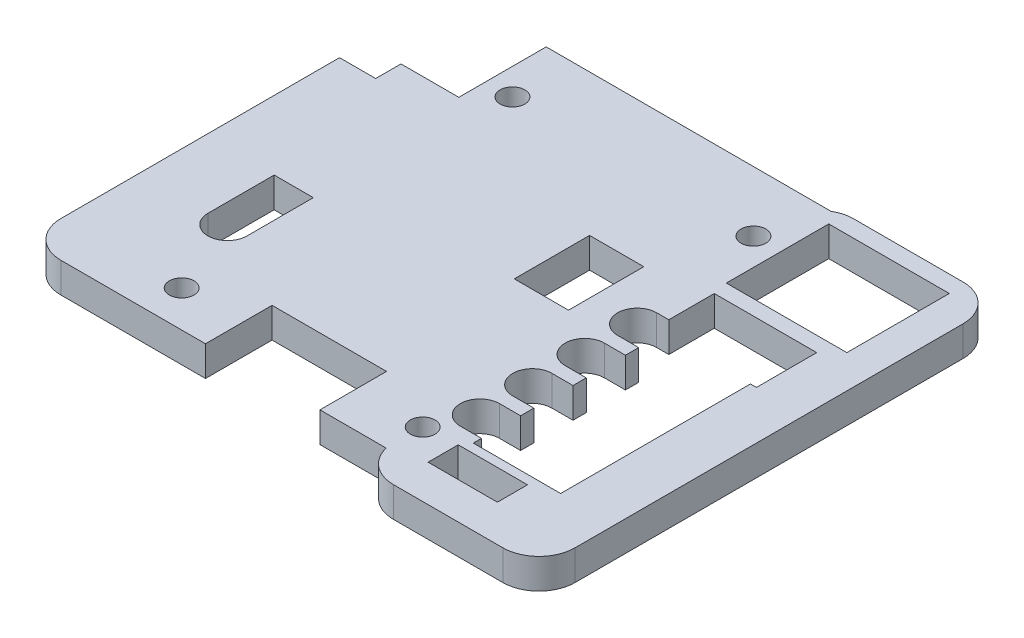
SolidWorks part; units mm, degrees
ref_plane "前视基准面" through (0, 0, 0) normal (0, 0, 1) x (1, 0, 0)
ref_plane "上视基准面" through (0, 0, 0) normal (0, 1, 0) x (1, 0, 0)
ref_plane "右视基准面" through (0, 0, 0) normal (1, 0, 0) x (0, 0, -1)
sketch "草图1" plane through (0, 0, 0) normal (0, 1, 0) x (1, 0, 0)
  line L0 (6, 0.3) -> (143.8, 0.3)
  line L1 (6, 0) -> (143.8, 0) construction
  line L2 (0, -6) -> (0, -68.8) construction
  line L3 (6, -74.8) -> (143.8, -74.8) construction
  line L4 (149.8, -6) -> (149.8, -68.8) construction
  line L5 (150.1, -6) -> (150.1, -68.8)
  line L6 (6, -75.1) -> (143.8, -75.1)
  line L7 (-0.3, -6) -> (-0.3, -68.8)
  arc A0 (143.8, 0) -> (149.8, -6) centre (143.8, -6) cw construction
  arc A1 (143.8, -74.8) -> (149.8, -68.8) centre (143.8, -68.8) ccw construction
  arc A2 (0, -68.8) -> (6, -74.8) centre (6, -68.8) ccw construction
  arc A3 (6, 0) -> (0, -6) centre (6, -6) ccw construction
  arc A4 (143.8, 0.3) -> (150.1, -6) centre (143.8, -6) cw
  arc A5 (143.8, -75.1) -> (150.1, -68.8) centre (143.8, -68.8) ccw
  arc A6 (-0.3, -68.8) -> (6, -75.1) centre (6, -68.8) ccw
  arc A7 (6, 0.3) -> (-0.3, -6) centre (6, -6) ccw
  point P7 (149.8, 0)
  point P12 (0, -74.8)
  point P15 (0, 0)
  dimension "D3" = 6
  dimension "D1" = 74.8
  dimension "D2" = 149.8
  dimension "D4" = 0.3
sketch "草图2" plane through (0, 0, 0) normal (0, -1, 0) x (-1, 0, 0)
  line L0 (-122.6, -55.35) -> (-108.9, -55.35) construction
  line L1 (-122.6, -69.85) -> (-108.9, -69.85) construction
  line L2 (-122.6, -69.85) -> (-122.6, -63.95) construction
  line L3 (-122.6, -63.95) -> (-108.9, -63.95) construction
  line L4 (-108.9, -69.85) -> (-108.9, -63.95) construction
  line L5 (-135.3, -1.25) -> (-35.3, -1.25) construction
  line L6 (-135.3, -1.25) -> (-135.3, -73.55) construction
  line L7 (-135.3, -73.55) -> (-35.3, -73.55) construction
  line L8 (-35.3, -1.25) -> (-35.3, -73.55) construction
  line L9 (-108.9, -61.25) -> (-108.9, -55.35) construction
  line L10 (-122.6, -61.25) -> (-108.9, -61.25) construction
  line L11 (-122.6, -61.25) -> (-122.6, -55.35) construction
  line L12 (-122.6, -46.75) -> (-108.9, -46.75) construction
  line L13 (-108.9, -52.65) -> (-108.9, -46.75) construction
  line L14 (-122.6, -52.65) -> (-108.9, -52.65) construction
  line L15 (-122.6, -52.65) -> (-122.6, -46.75) construction
  line L16 (-122.6, -38.15) -> (-108.9, -38.15) construction
  line L17 (-108.9, -44.05) -> (-108.9, -38.15) construction
  line L18 (-122.6, -44.05) -> (-108.9, -44.05) construction
  line L19 (-122.6, -44.05) -> (-122.6, -38.15) construction
  line L20 (0, -6) -> (0, -68.8) construction
  line L21 (-35.3, -73.55) -> (-0.8, -73.55) construction
  line L22 (-120.25, -26.65) -> (-111.25, -26.65) construction
  line L23 (-120.25, -26.65) -> (-120.25, -33.15) construction
  line L24 (-120.25, -33.15) -> (-111.25, -33.15) construction
  line L25 (-111.25, -26.65) -> (-111.25, -33.15) construction
  line L26 (-85.8, -48.75) -> (-81.1, -48.75) construction
  line L27 (-85.8, -48.75) -> (-85.8, -58.15) construction
  line L28 (-85.8, -58.15) -> (-81.1, -58.15) construction
  line L29 (-81.1, -48.75) -> (-81.1, -58.15) construction
  line L30 (-71.5, -48.65) -> (-68.2, -48.65) construction
  line L31 (-71.5, -48.65) -> (-71.5, -57.55) construction
  line L32 (-71.5, -57.55) -> (-68.2, -57.55) construction
  line L33 (-68.2, -48.65) -> (-68.2, -57.55) construction
  line L34 (-43.1, -45.05) -> (-38.6, -45.05) construction
  line L35 (-43.1, -45.05) -> (-43.1, -59.05) construction
  line L36 (-43.1, -59.05) -> (-38.6, -59.05) construction
  line L37 (-38.6, -45.05) -> (-38.6, -59.05) construction
  line L38 (-45.3, -61.55) -> (-40.8, -61.55) construction
  line L39 (-45.3, -61.55) -> (-45.3, -66.05) construction
  line L40 (-45.3, -66.05) -> (-40.8, -66.05) construction
  line L41 (-40.8, -61.55) -> (-40.8, -66.05) construction
  line L42 (-0.8, -73.55) -> (-0.8, -1.25) construction
  line L43 (-0.8, -1.25) -> (-35.3, -1.25) construction
  line L44 (-149.8, -6) -> (-149.8, -68.8) construction
  line L45 (-30.8, -34.65) -> (-27.3, -34.65) construction
  line L46 (-30.8, -34.65) -> (-30.8, -40.15) construction
  line L47 (-30.8, -40.15) -> (-27.3, -40.15) construction
  line L48 (-27.3, -34.65) -> (-27.3, -40.15) construction
  line L49 (-120.75, -33.65) -> (-110.75, -33.65)
  line L50 (-110.75, -26.15) -> (-110.75, -33.65)
  line L51 (-120.75, -26.15) -> (-110.75, -26.15)
  line L52 (-120.75, -26.15) -> (-120.75, -33.65)
  line L53 (-86.3, -48.25) -> (-86.3, -58.65)
  line L54 (-86.3, -58.65) -> (-80.6, -58.65)
  line L55 (-80.6, -48.25) -> (-80.6, -58.65)
  line L56 (-86.3, -48.25) -> (-80.6, -48.25)
  line L57 (-72, -48.15) -> (-72, -58.05)
  line L58 (-72, -58.05) -> (-67.7, -58.05)
  line L59 (-67.7, -48.15) -> (-67.7, -58.05)
  line L60 (-72, -48.15) -> (-67.7, -48.15)
  line L61 (-31.3, -34.15) -> (-31.3, -40.65)
  line L62 (-31.3, -40.65) -> (-26.8, -40.65)
  line L63 (-26.8, -34.15) -> (-26.8, -40.65)
  line L64 (-31.3, -34.15) -> (-26.8, -34.15)
  line L65 (-43.6, -44.55) -> (-43.6, -59.55)
  line L66 (-43.6, -59.55) -> (-38.1, -59.55)
  line L67 (-38.1, -44.55) -> (-38.1, -59.55)
  line L68 (-43.6, -44.55) -> (-38.1, -44.55)
  line L69 (-45.8, -61.05) -> (-45.8, -66.55)
  line L70 (-45.8, -66.55) -> (-40.3, -66.55)
  line L71 (-40.3, -61.05) -> (-40.3, -66.55)
  line L72 (-45.8, -61.05) -> (-40.3, -61.05)
  line L73 (-122.9, -44.35) -> (-108.6, -44.35)
  line L74 (-108.6, -44.35) -> (-108.6, -37.85)
  line L75 (-122.9, -37.85) -> (-108.6, -37.85)
  line L76 (-122.9, -44.35) -> (-122.9, -37.85)
  line L77 (-122.9, -52.95) -> (-108.6, -52.95)
  line L78 (-108.6, -52.95) -> (-108.6, -46.45)
  line L79 (-122.9, -46.45) -> (-108.6, -46.45)
  line L80 (-122.9, -52.95) -> (-122.9, -46.45)
  line L81 (-122.9, -61.55) -> (-108.6, -61.55)
  line L82 (-108.6, -61.55) -> (-108.6, -55.05)
  line L83 (-122.9, -55.05) -> (-108.6, -55.05)
  line L84 (-122.9, -61.55) -> (-122.9, -55.05)
  line L85 (-122.9, -70.15) -> (-108.6, -70.15)
  line L86 (-108.6, -70.15) -> (-108.6, -63.65)
  line L87 (-122.9, -63.65) -> (-108.6, -63.65)
  line L88 (-122.9, -70.15) -> (-122.9, -63.65)
  circle A0 centre (-103.2, -9.35) radius 1.65 construction
  circle A1 centre (-103.2, -64.25) radius 1.65 construction
  circle A2 centre (-63.2, -64.25) radius 1.65 construction
  circle A3 centre (-63.2, -9.35) radius 1.65 construction
  circle A4 centre (-130.8, -5.6) radius 1.25 construction
  circle A5 centre (-131.1, -55.65) radius 1.25 construction
  circle A6 centre (-47.7, -4.85) radius 1.25 construction
  circle A7 centre (-48.1, -68.75) radius 1.25 construction
  circle A8 centre (-22.8, -70.3) radius 1.25 construction
  circle A9 centre (-5.05, -71.05) radius 1.25 construction
  circle A10 centre (-5.05, -3.25) radius 1.25 construction
  circle A11 centre (-19, -37.4) radius 3.6 construction
  circle A12 centre (-103.2, -9.35) radius 2.05
  circle A13 centre (-63.2, -9.35) radius 2.05
  circle A14 centre (-63.2, -64.25) radius 2.05
  circle A15 centre (-103.2, -64.25) radius 2.05
  circle A16 centre (-19, -37.4) radius 4.1
  circle A17 centre (-130.8, -5.6) radius 1.75
  circle A18 centre (-131.1, -55.65) radius 1.75
  circle A19 centre (-48.1, -68.75) radius 1.75
  circle A20 centre (-22.8, -70.3) radius 1.75
  circle A21 centre (-5.05, -71.05) radius 1.75
  circle A22 centre (-5.05, -3.25) radius 1.75
  circle A23 centre (-47.7, -4.85) radius 1.75
  point P22 (0, -37.4)
  point P23 (-135.3, -37.4)
  point P28 (-115.75, -33.15)
  point P29 (-115.75, -38.15)
  point P30 (-111.25, -29.9)
  point P31 (-108.9, -41.1)
  point P79 (-0.8, -37.4)
  point P81 (-27.3, -37.4)
  dimension "D21" = 3.3
  dimension "D34" = 2.5
  dimension "D53" = 7.2
  dimension "D1" = 13.7
  dimension "D2" = 5.9
  dimension "D3" = 72.3
  dimension "D4" = 3.7
  dimension "D5" = 12.7
  dimension "D7" = 14.5
  dimension "D8" = 100
  dimension "D9" = 2.7
  dimension "D10" = 9
  dimension "D11" = 6.5
  dimension "D12" = 11.2
  dimension "D13" = 15.4
  dimension "D14" = 9.4
  dimension "D15" = 4.7
  dimension "D16" = 23.1
  dimension "D17" = 3.3
  dimension "D18" = 8.9
  dimension "D19" = 16
  dimension "D20" = 37.4
  dimension "D22" = 8.1
  dimension "D23" = 32.1
  dimension "D24" = 40
  dimension "D25" = 9.3
  dimension "D26" = 14
  dimension "D27" = 4.5
  dimension "D28" = 4.5
  dimension "D29" = 4.5
  dimension "D30" = 3.3
  dimension "D31" = 5.5
  dimension "D32" = 7.5
  dimension "D33" = 14.5
  dimension "D35" = 34.5
  dimension "D36" = 2
  dimension "D37" = 4.25
  dimension "D38" = 2.5
  dimension "D39" = 3.25
  dimension "D40" = 22
  dimension "D41" = 4.8
  dimension "D42" = 12.8
  dimension "D43" = 3.6
  dimension "D44" = 12.4
  dimension "D45" = 4.35
  dimension "D46" = 4.5
  dimension "D47" = 4.2
  dimension "D48" = 17.9
  dimension "D49" = 18.2
  dimension "D50" = 3.5
  dimension "D51" = 5.5
  dimension "D52" = 8.3
  dimension "D54" = 0.4
  dimension "D55" = 0.5
  dimension "D56" = 0.5
  dimension "D57" = 0.5
  dimension "D58" = 0.3
  dimension "D6" = 4
sketch "草图3" plane through (0, 0, 0) normal (0, 1, 0) x (1, 0, 0)
  line L0 (135.3, -1.25) -> (135.3, -73.55) construction
  line L1 (143.8, 0) -> (135.3, 0)
  line L2 (149.8, -6) -> (149.8, -68.8)
  line L3 (143.8, -74.8) -> (135.3, -74.8)
  line L4 (135.3, 0) -> (135.3, -74.8)
  line L5 (6, -74.8) -> (143.8, -74.8) construction
  arc A0 (143.8, 0) -> (149.8, -6) centre (143.8, -6) cw
  arc A1 (149.8, -68.8) -> (143.8, -74.8) centre (143.8, -68.8) cw
  point P17 (149.8, 0)
  dimension "D1" = 6
sketch "草图4" plane through (0, 0, 0) normal (0, 1, 0) x (1, 0, 0)
  line L0 (122.9, -62.85) -> (108.6, -62.85)
  line L1 (122.6, -63.15) -> (108.9, -63.15) construction
  line L2 (122.6, -63.15) -> (122.6, -70.65) construction
  line L3 (122.6, -70.65) -> (108.9, -70.65) construction
  line L4 (108.9, -63.15) -> (108.9, -70.65) construction
  line L5 (122.6, -69.85) -> (122.6, -63.95) construction
  line L6 (108.6, -62.85) -> (108.6, -70.95)
  line L7 (108.9, -69.85) -> (108.9, -63.95) construction
  line L8 (122.6, -54.55) -> (108.9, -54.55) construction
  line L9 (108.9, -54.55) -> (108.9, -62.05) construction
  line L10 (122.6, -62.05) -> (108.9, -62.05) construction
  line L11 (122.6, -54.55) -> (122.6, -62.05) construction
  line L12 (122.6, -45.95) -> (108.9, -45.95) construction
  line L13 (108.9, -45.95) -> (108.9, -53.45) construction
  line L14 (122.6, -53.45) -> (108.9, -53.45) construction
  line L15 (122.6, -45.95) -> (122.6, -53.45) construction
  line L16 (122.6, -37.35) -> (108.9, -37.35) construction
  line L17 (108.9, -37.35) -> (108.9, -44.85) construction
  line L18 (122.6, -44.85) -> (108.9, -44.85) construction
  line L19 (122.6, -37.35) -> (122.6, -44.85) construction
  line L20 (122.9, -70.95) -> (108.6, -70.95)
  line L21 (122.9, -62.85) -> (122.9, -70.95)
  line L22 (122.9, -54.25) -> (108.6, -54.25)
  line L23 (108.6, -54.25) -> (108.6, -62.35)
  line L24 (122.9, -62.35) -> (108.6, -62.35)
  line L25 (122.9, -54.25) -> (122.9, -62.35)
  line L26 (122.9, -45.65) -> (108.6, -45.65)
  line L27 (108.6, -45.65) -> (108.6, -53.75)
  line L28 (122.9, -53.75) -> (108.6, -53.75)
  line L29 (122.9, -45.65) -> (122.9, -53.75)
  line L30 (122.9, -37.05) -> (108.6, -37.05)
  line L31 (108.6, -37.05) -> (108.6, -45.15)
  line L32 (122.9, -45.15) -> (108.6, -45.15)
  line L33 (122.9, -37.05) -> (122.9, -45.15)
  point P11 (108.9, -66.9)
  point P12 (108.9, -66.9)
  dimension "D1" = 7.5
  dimension "D3" = 1.1
  dimension "D4" = 0.3
  dimension "D2" = 4
extrude "拉伸-薄壁1" add sketch "草图2" along normal blind 5 thin contours A13 | A12 | A14 | A15 thin type one direction wall 4
sketch "草图6" plane through (0, 0, 0) normal (0, 1, 0) x (1, 0, 0)
  line L0 (127.2, 1.45) -> (109.0462, 1.45)
  line L1 (133.2, -4.55) -> (133.2, -68.95)
  line L2 (127.2, -74.95) -> (109.0462, -74.95)
  line L3 (33.4345, -36.75) -> (43.3021, -36.75) construction
  line L4 (63.2, 0.65) -> (106.0528, 0.65)
  line L6 (63.2, 0.65) -> (45.7, 0.65)
  line L10 (122.9, -70.95) -> (108.6, -70.95) construction
  line L11 (108.6, -62.85) -> (108.6, -70.95) construction
  line L12 (43.2, -1.85) -> (43.2, -64.3)
  line L13 (103.2, -70.3) -> (49.2, -70.3)
  circle A1 centre (103.2, -64.25) radius 6.05 construction
  arc A3 (133.2, -4.55) -> (127.2, 1.45) centre (127.2, -4.55) ccw
  arc A4 (109.0462, -74.95) -> (103.2, -70.3) centre (109.0462, -68.95) cw
  circle A5 centre (63.2, -64.25) radius 6.05 construction
  arc A6 (133.2, -68.95) -> (127.2, -74.95) centre (127.2, -68.95) cw
  arc A7 (109.0462, 1.45) -> (106.0528, 0.65) centre (109.0462, -4.55) ccw
  arc A9 (43.2, -64.3) -> (49.2, -70.3) centre (49.2, -64.3) ccw
  circle A10 centre (103.2, -9.35) radius 2.05 construction
  circle A11 centre (103.2, -64.25) radius 2.05 construction
  circle A12 centre (63.2, -64.25) radius 2.05 construction
  circle A13 centre (103.2, -9.35) radius 2.05
  circle A14 centre (103.2, -64.25) radius 2.05
  circle A15 centre (63.2, -64.25) radius 2.05
  circle A16 centre (63.2, -9.35) radius 2.05 construction
  circle A17 centre (63.2, -9.35) radius 2.05
  arc A18 (45.7, 0.65) -> (43.2, -1.85) centre (45.7, -1.85) ccw
  point P37 (105.6, -74.95)
  point P42 (130.9, -6.15)
  dimension "D6" = 6
  dimension "D7" = 5
  dimension "D8" = 6
  dimension "D9" = 6
  dimension "D10" = 6
  dimension "D11" = 6
  dimension "D2" = 27.5
  dimension "D3" = 4
  dimension "D4" = 3
  dimension "D5" = 20
  dimension "D12" = 30
  dimension "D13" = 10
extrude "凸台-拉伸1" add sketch "草图6" against normal up to surface (5 mm away) up to face at (97.15, -5, 9.35)
sketch "草图7" plane through (0, -5, 3) normal (0, -1, 0) x (1, 0, 0)
  line L9 (80.466, 15.85) -> (96.6871, 15.85) construction
  line L43 (107.2, -14.628) -> (107.2, -27.7853) construction
  line L44 (108.9, 22) -> (108.9, 67) construction
  line L45 (122.6, 67) -> (108.9, 67) construction
  line L46 (122.6, 22) -> (122.6, 67) construction
  line L47 (122.6, 22) -> (108.9, 22) construction
  line L48 (120.2, 9.55) -> (113.2, 9.55)
  line L49 (120.2, 4.55) -> (120.2, 9.55)
  line L50 (113.2, 4.55) -> (120.2, 4.55)
  line L51 (113.2, 9.55) -> (113.2, 4.55)
  line L52 (80.4, 48.65) -> (80.4, 33.65)
  line L53 (85.4, 48.65) -> (80.4, 48.65)
  line L54 (97.9, 36.55) -> (89.9, 36.55)
  line L55 (97.9, 25.55) -> (97.9, 36.55)
  line L56 (89.9, 25.55) -> (97.9, 25.55)
  line L57 (89.9, 36.55) -> (89.9, 25.55)
  line L58 (66.4, 33.65) -> (80.4, 33.65)
  line L59 (50.4, 54.65) -> (50.4, 33.65)
  line L60 (85.4, 54.65) -> (50.4, 54.65)
  line L61 (85.4, 48.65) -> (85.4, 54.65)
  line L62 (47.4, 10.15) -> (66.4, 10.15)
  line L63 (47.4, 33.65) -> (47.4, 10.15)
  line L64 (50.4, 33.65) -> (47.4, 33.65)
  line L65 (66.4, 10.15) -> (66.4, 15.35)
  line L66 (66.4, 24.35) -> (72.4, 24.35)
  line L67 (66.4, 24.35) -> (66.4, 33.65)
  line L68 (72.4, 15.35) -> (66.4, 15.35)
  line L69 (122.9, 21.7) -> (122.9, 67.3)
  line L70 (122.9, 67.3) -> (108.6, 67.3)
  line L71 (72.4, 24.35) -> (72.4, 15.35)
  line L72 (92.2, 15.35) -> (75.2, 15.35)
  line L73 (92.2, 23.55) -> (92.2, 15.35)
  line L74 (75.2, 23.55) -> (92.2, 23.55)
  line L75 (107.7, 23.55) -> (107.7, 15.35)
  line L76 (98.2, 23.55) -> (107.7, 23.55)
  line L77 (98.2, 15.35) -> (98.2, 23.55)
  line L78 (107.7, 15.35) -> (98.2, 15.35)
  line L79 (75.2, 15.35) -> (75.2, 23.55)
  line L80 (108.6, 21.7) -> (108.6, 67.3)
  line L81 (122.9, 21.7) -> (108.6, 21.7)
  circle A0 centre (103.2, 61.25) radius 2.05 construction
  circle A1 centre (103.2, 61.25) radius 2.05
  circle A5 centre (59.2, 61.25) radius 2.05
  circle A6 centre (103.2, 61.25) radius 2.05
extrude "切除-拉伸1" [suppressed] cut sketch "草图7" against normal blind 5 contours L81 L69 L70 L80 | L78 L75 L76 L77 | L54 L57 L56 L55 | L79 L72 L73 L74 | L71 L66 L67 L58 L52 L53 L61 L60 L59 L64 L63 L62 L65 L68
sketch "草图8" plane through (0, 0, 0) normal (0, -1, 0) x (1, 0, 0)
  line L3 (106.2, 28.95) -> (106.2, 55.65) construction
  line L6 (133.2, 68.95) -> (133.2, 4.55) construction
  line L7 (109.0462, 74.95) -> (127.2, 74.95) construction
  line L9 (80.466, -18.85) -> (96.6871, -18.85) construction
  line L10 (107.2, 11.628) -> (107.2, 24.7853) construction
  line L14 (5.1637, 36.85) -> (19.0276, 36.85) construction
  line L15 (106.2, 60.7) -> (109.7, 60.7)
  line L18 (63.2, 64.25) -> (46.0308, 64.25) construction
  line L19 (67.2, 40.45) -> (49.2, 40.45)
  line L20 (106.2, 54.2) -> (109.7, 54.2)
  line L22 (67.2, 13.45) -> (67.2, 40.45)
  line L23 (49.2, 13.45) -> (67.2, 13.45)
  line L24 (49.2, 40.45) -> (49.2, 13.45)
  line L25 (98.5, 35.95) -> (89.5, 35.95)
  line L26 (98.5, 23.45) -> (98.5, 35.95)
  line L27 (89.5, 23.45) -> (98.5, 23.45)
  line L28 (89.5, 35.95) -> (89.5, 23.45)
  line L29 (108.2, 30.95) -> (125.2, 30.95) construction
  line L30 (128.2, 18.45) -> (108.2, 18.45)
  line L31 (128.2, 2.45) -> (128.2, 18.45)
  line L32 (108.2, 2.45) -> (128.2, 2.45)
  line L37 (108.2, 18.45) -> (108.2, 2.45)
  line L38 (125.2, 20.95) -> (125.2, 30.95)
  line L47 (125.2, 30.95) -> (124.2, 30.95)
  line L48 (108.2, 30.95) -> (108.2, 20.95)
  line L49 (108.2, 30.95) -> (109.7, 30.95)
  line L50 (125.2, 20.95) -> (108.2, 20.95)
  line L51 (111.7, 64.75) -> (122.2, 64.75)
  line L52 (122.2, 62.75) -> (122.2, 69.95)
  line L53 (124.2, 30.95) -> (124.2, 63.75)
  line L54 (109.7, 63.75) -> (124.2, 63.75)
  line L55 (111.7, 69.95) -> (122.2, 69.95)
  line L56 (111.7, 69.95) -> (111.7, 62.75)
  line L57 (109.7, 30.95) -> (109.7, 63.75)
  line L58 (75.2, 64.35) -> (89.2, 64.35)
  line L59 (75.2, 73.35) -> (75.2, 64.35)
  line L60 (89.2, 73.35) -> (75.2, 73.35)
  line L61 (89.2, 64.35) -> (89.2, 73.35)
  line L62 (106.2, 51.8) -> (109.7, 51.8)
  line L63 (106.2, 45.3) -> (109.7, 45.3)
  line L64 (106.2, 42.9) -> (109.7, 42.9)
  line L65 (106.2, 36.4) -> (109.7, 36.4)
  line L66 (106.2, 34) -> (109.7, 34)
  line L67 (106.2, 27.5) -> (108.2, 27.5)
  line L68 (109.7, 34) -> (109.7, 27.5)
  line L69 (109.7, 27.5) -> (108.2, 27.5)
  line L70 (109.7, 36.4) -> (109.7, 42.9)
  line L71 (109.7, 45.3) -> (109.7, 51.8)
  line L72 (109.7, 54.2) -> (109.7, 60.7)
  circle A1 centre (57.9, 42.45) radius 3.25
  circle A2 centre (103.2, 9.35) radius 2.4
  circle A3 centre (106.2, 57.45) radius 3.25
  circle A4 centre (63.2, 9.35) radius 2.4
  circle A5 centre (103.2, 64.25) radius 2.4 construction
  circle A10 centre (106.2, 48.55) radius 3.25
  circle A11 centre (63.2, 64.25) radius 2.4 construction
  circle A14 centre (106.2, 39.65) radius 3.25
  circle A15 centre (106.2, 30.75) radius 3.25
  dimension "D7" = 27.5
  dimension "D1" = 10
  dimension "D3" = 8.9
  dimension "D2" = 27
  dimension "D4" = 8.9
  dimension "D5" = 8.9
  dimension "D6" = 17.5
  dimension "D8" = 20
extrude "切除-拉伸2" [suppressed] cut sketch "草图8" along normal through all
sketch "草图10" plane through (0, 0, 0) normal (0, -1, 0) x (1, 0, 0)
  line L0 (67.2, 40.45) -> (49.2, 40.45)
  line L1 (49.2, 40.45) -> (49.2, 13.45)
  line L2 (49.2, 13.45) -> (67.2, 13.45)
  line L3 (67.2, 13.45) -> (67.2, 40.45)
sketch "草图9" plane through (0, -5, 0) normal (0, -1, 0) x (1, 0, 0)
  line L0 (58.8, 13.85) -> (58.8, 1.85)
  line L2 (58.8, 1.85) -> (45.8, 1.85)
  line L3 (45.8, 1.85) -> (45.8, 13.85)
  line L4 (45.8, 13.85) -> (58.8, 13.85)
  circle A0 centre (63.2, 9.35) radius 2.05 construction
  circle A1 centre (63.2, 9.35) radius 2.05 construction
  dimension "D1" = 13
  dimension "D2" = 4.5
  dimension "D3" = 4.4
  dimension "D4" = 12
extrude "切除-拉伸3" [suppressed] cut sketch "草图9" against normal through all
extrude "切除-拉伸5_电源模块(一般不用，焊接模块时才需要)" [suppressed] cut sketch "草图10" along normal blind 2
sketch "草图11" plane through (0, -5, 5) normal (0, -1, 0) x (1, 0, 0)
  line L3 (106.0528, -5.65) -> (45.7, -5.65) construction
  line L9 (80.466, -18.85) -> (96.6871, -18.85) construction
  line L10 (107.2, 11.628) -> (107.2, 24.7853) construction
  line L19 (106.2, -55.55) -> (106.2, -28.85) construction
  line L54 (63.2, 4.35) -> (46.0308, 4.35) construction
  line L55 (108.2, 25.85) -> (125.2, 25.85) construction
  line L56 (45.8, 13.05) -> (49.2, 13.05)
  line L57 (45.8, 13.05) -> (45.8, 6.35)
  line L58 (39.8, 13.05) -> (45.8, 13.05)
  line L59 (39.8, 6.35) -> (39.8, 13.05)
  line L60 (45.8, 6.35) -> (39.8, 6.35)
  line L61 (45.8, -3.15) -> (58.8, -3.15)
  line L62 (45.8, 8.85) -> (45.8, -3.15)
  line L63 (73.2, 54.25) -> (92.2, 54.25)
  line L64 (73.2, 66.25) -> (73.2, 54.25)
  line L65 (92.2, 66.25) -> (73.2, 66.25)
  line L66 (92.2, 54.25) -> (92.2, 66.25)
  line L67 (127.7, 13.35) -> (107.7, 13.35)
  line L68 (127.7, -3.65) -> (127.7, 13.35)
  line L69 (107.7, -3.65) -> (127.7, -3.65)
  line L70 (107.7, 13.35) -> (107.7, -3.65)
  line L71 (58.8, 8.85) -> (45.8, 8.85)
  line L72 (58.8, -3.15) -> (58.8, 8.85)
  line L73 (98.5, 30.35) -> (89.5, 30.35)
  line L74 (98.5, 17.85) -> (98.5, 30.35)
  line L75 (89.5, 17.85) -> (98.5, 17.85)
  line L76 (89.5, 30.35) -> (89.5, 17.85)
  line L77 (61.15, 46.35) -> (61.15, 35.35)
  line L78 (54.65, 46.35) -> (54.65, 35.35)
  line L79 (106.2, 56) -> (109.7, 56)
  line L80 (106.2, 49.5) -> (109.7, 49.5)
  line L81 (106.2, 47.3) -> (109.7, 47.3)
  line L82 (106.2, 40.8) -> (109.7, 40.8)
  line L83 (109.7, 38.6) -> (106.2, 38.6)
  line L84 (109.7, 32.1) -> (109.7, 38.6)
  line L85 (106.2, 32.1) -> (109.7, 32.1)
  line L86 (106.2, 29.9) -> (109.7, 29.9)
  line L87 (106.2, 23.4) -> (108.2, 23.4)
  line L88 (125.2, 15.85) -> (125.2, 25.85)
  line L89 (108.7, 58.85) -> (120.2, 58.85)
  line L90 (67.2, 35.35) -> (49.2, 35.35)
  line L91 (67.2, 8.35) -> (67.2, 35.35)
  line L92 (120.2, 57.35) -> (120.2, 63.85)
  line L93 (124.2, 57.35) -> (120.2, 57.35)
  line L94 (124.2, 25.85) -> (124.2, 57.35)
  line L95 (125.2, 25.85) -> (124.2, 25.85)
  line L96 (49.2, 8.35) -> (67.2, 8.35)
  line L97 (109.7, 57.35) -> (124.2, 57.35)
  line L98 (108.7, 63.85) -> (120.2, 63.85)
  line L99 (108.2, 25.85) -> (108.2, 15.85)
  line L100 (49.2, 35.35) -> (49.2, 8.35)
  line L101 (108.7, 63.85) -> (108.7, 57.35)
  line L102 (109.7, 25.85) -> (109.7, 57.35)
  line L103 (108.2, 25.85) -> (109.7, 25.85)
  line L104 (125.2, 15.85) -> (108.2, 15.85)
  circle A13 centre (63.2, 4.35) radius 2.4 construction
  circle A14 centre (103.2, 4.35) radius 2.4 construction
  circle A15 centre (57.9, 46.35) radius 3.25
  circle A16 centre (106.2, 52.75) radius 3.25
  circle A17 centre (106.2, 44.05) radius 3.25
  circle A18 centre (106.2, 35.35) radius 3.25
  circle A19 centre (106.2, 26.65) radius 3.25
  circle A20 centre (63.2, 59.25) radius 2.4
  circle A21 centre (103.2, 59.25) radius 2.4
  dimension "D1" = 52
extrude "切除-拉伸4" cut sketch "草图11" against normal through all contours L98 L101 L89 L92 | L79 A16 L80 L102 | L81 A17 L82 L102 | L83 A18 L85 L84 | L86 A19 L103 L102 | L99 A19 L87 | L100 L56 L57 L71 | L77 A15 L78 L90 | L63 L66 L65 L64 | L97 L102 L103 L99 L104 L88 L95 L94 | A16 | A17 | A18 | A19 | L74 L73 L76 L75 | L67 L70 L69 L68 | A15 | L72 L71 L62 L61 | L57 L60 L59 L58 region at (47.5, -5, 15.95) region at (57.9, -5, 44.6049) region at (114.45, -5, 66.35) region at (107.95, -5, 60.9262) region at (109.6262, -5, 49.05) region at (109.6262, -5, 40.35) region at (108.9903, -5, 33.7511) region at (107.7112, -5, 28.6021)
sketch "草图12" plane through (0, -5, 0) normal (0, -1, 0) x (1, 0, 0)
  line L0 (58.8, 1.85) -> (58.8, -0.65)
  line L1 (106.0528, -0.65) -> (45.7, -0.65) construction
  line L2 (43.2, 1.85) -> (43.2, 11.35) construction
  line L3 (45.8, 11.35) -> (43.2, 11.35) construction
  line L4 (45.8, 11.35) -> (45.8, 1.85) construction
  line L5 (45.8, 1.85) -> (58.8, 1.85) construction
  line L6 (106.0528, -0.65) -> (45.7, -0.65)
  line L7 (43.2, 1.85) -> (43.2, 11.35)
  line L8 (45.8, 11.35) -> (43.2, 11.35)
  line L9 (45.8, 11.35) -> (45.8, 1.85)
  line L10 (45.8, 1.85) -> (58.8, 1.85)
  arc A0 (43.2, 1.85) -> (45.7, -0.65) centre (45.7, 1.85) ccw construction
  arc A1 (43.2, 1.85) -> (45.7, -0.65) centre (45.7, 1.85) ccw
extrude "切除-拉伸5" cut sketch "草图12" against normal through all contours L7 A1 L6 L0 L10 L9 L8 region at (58.6032, -5, 0.6)
equation "\"D1@草图3\"=\"D3@草图1\""
